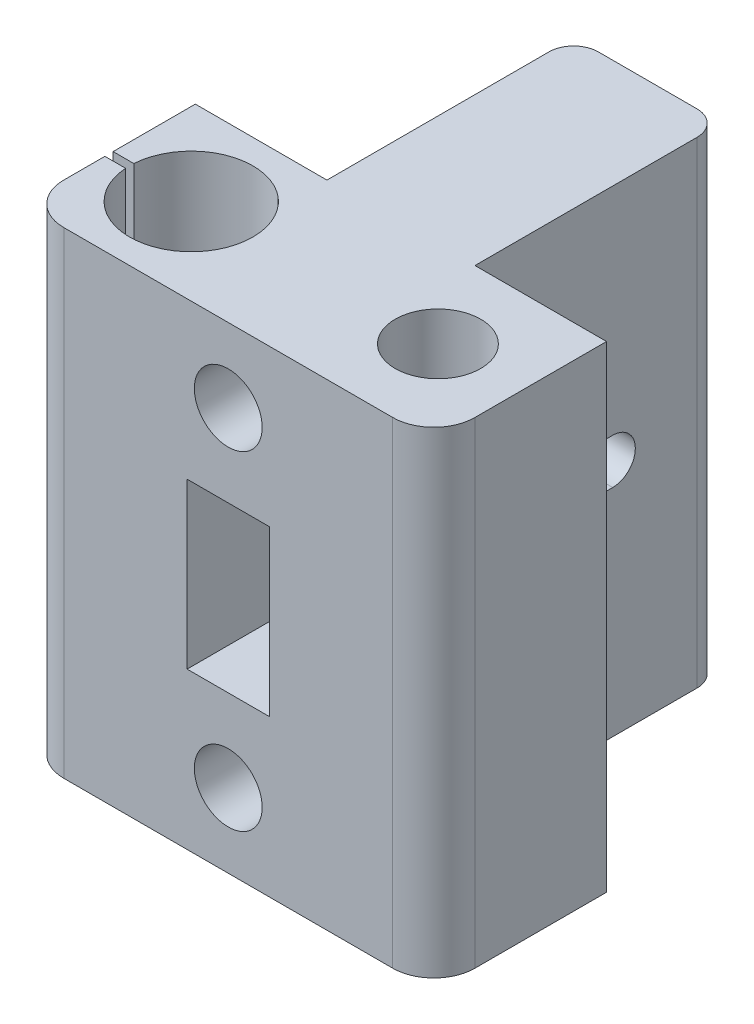
SolidWorks part; units mm, degrees
ref_plane "Front Plane" through (0, 0, 0) normal (0, 0, 1) x (1, 0, 0)
ref_plane "Top Plane" through (0, 0, 0) normal (0, 1, 0) x (1, 0, 0)
ref_plane "Right Plane" through (0, 0, 0) normal (1, 0, 0) x (0, 0, -1)
sketch "Sketch1" plane through (0, 0, 0) normal (0, 1, 0) x (1, 0, 0)
  line L1 (-25, 10.5) -> (25, 10.5)
  line L2 (-25, 10.5) -> (-25, -10.5)
  line L3 (-25, -10.5) -> (25, -10.5)
  line L4 (25, 10.5) -> (25, -10.5)
  line L5 (-25, 10.5) -> (25, -10.5) construction
  line L6 (-25, -10.5) -> (25, 10.5) construction
  point P0 (0, 0)
  dimension "D1" = 21
  dimension "D2" = 50
extrude "Boss-Extrude1" add sketch "Sketch1" along normal blind 58
sketch "Sketch3" plane through (0, 58, 0) normal (0, 1, 0) x (1, 0, 0)
  line L0 (-15, 0) -> (15, 0) construction
  circle A0 centre (-15, 0) radius 7.5
  dimension "D1" = 15
  dimension "D2" = 30
extrude "Cut-Extrude1" cut sketch "Sketch3" against normal blind 24 contours A0
sketch "Sketch4" plane through (0, 58, 0) normal (0, 1, 0) x (1, 0, 0)
  line L0 (-15, 0) -> (15, 0) construction
  circle A0 centre (15, 0) radius 5.2
  dimension "D1" = 10.4
extrude "Cut-Extrude2" cut sketch "Sketch4" against normal up to next
sketch "Sketch5" plane through (0, 0, 0) normal (0, -1, 0) x (1, 0, 0)
  circle A1 centre (-15, 0) radius 7.5
  circle A2 centre (-15, 0) radius 7.5
  dimension "D1" = 0
extrude "Cut-Extrude3" cut sketch "Sketch5" against normal blind 24
sketch "Sketch6" plane through (0, 0, 0) normal (0, -1, 0) x (1, 0, 0)
  circle A0 centre (-15, 0) radius 4.5
extrude "Cut-Extrude4" cut sketch "Sketch6" against normal up to next
sketch "Sketch8" plane through (0, 0, 10.5) normal (0, 0, 1) x (1, 0, 0)
  line L0 (-25, 29) -> (25, 29) construction
  line L1 (-25, 58) -> (-25, 0) construction
  line L2 (25, 58) -> (25, 0) construction
  line L3 (0, 58) -> (0, 0) construction
  line L4 (-25, 58) -> (25, 58) construction
  line L6 (-5, 19) -> (5, 19)
  line L7 (-5, 19) -> (-5, 39)
  line L8 (-5, 39) -> (5, 39)
  line L9 (5, 19) -> (5, 39)
  line L10 (-5, 19) -> (5, 39) construction
  line L11 (-5, 39) -> (5, 19) construction
  point P11 (0, 29)
  dimension "D1" = 20
  dimension "D2" = 10
extrude "Cut-Extrude5" cut sketch "Sketch8" against normal up to next
sketch "Sketch10" plane through (0, 0, -10.5) normal (0, 0, -1) x (-1, 0, 0)
  line L0 (-25, 29) -> (25, 29) construction
  line L1 (-25, 58) -> (-25, 0) construction
  line L2 (25, 58) -> (25, 0) construction
  line L3 (0, 58) -> (0, 0) construction
  line L4 (-25, 58) -> (25, 58) construction
sketch "Sketch11" plane through (0, 0, -10.5) normal (0, 0, -1) x (-1, 0, 0)
  line L0 (-25, 29) -> (25, 29) construction
  line L1 (9, 39) -> (5, 39)
  line L2 (9, 39) -> (9, 19)
  line L3 (9, 19) -> (5, 19)
  line L4 (5, 39) -> (5, 19)
  line L5 (9, 39) -> (5, 19) construction
  line L6 (9, 19) -> (5, 39) construction
  line L7 (0, 58) -> (0, 0) construction
  line L8 (0, 58) -> (0, 0)
  line L9 (-9, 19) -> (-5, 19)
  line L10 (-5, 39) -> (-5, 19)
  line L11 (-9, 39) -> (-5, 39)
  line L12 (-9, 39) -> (-9, 19)
  point P0 (7, 29)
  line M7 (-5, 19) -> (-5, 39)
  line M9 (5, 39) -> (5, 19)
  dimension "D1" = 5
  dimension "D2" = 4
  dimension "D3" = 20
extrude "Boss-Extrude2" add sketch "Sketch11" along normal blind 26 contours L1 L4 L3 L2 M9 | L11 L12 L9 L10 M7 region at (-7, 29, -10.5) region at (7, 29, -10.5)
sketch "Sketch12" plane through (0, 0, -36.5) normal (0, 0, -1) x (-1, 0, 0)
  line L1 (9, 19) -> (-9, 19)
  line L2 (9, 19) -> (9, 39)
  line L3 (9, 39) -> (-9, 39)
  line L4 (-9, 19) -> (-9, 39)
extrude "Boss-Extrude3" add sketch "Sketch12" along normal blind 4
sketch "Sketch13" plane through (9, 0, 0) normal (1, 0, 0) x (0, 0, -1)
  line L3 (10.5, 29) -> (40.5, 29) construction
  line L4 (10.5, 39) -> (10.5, 19) construction
  line L5 (40.5, 39) -> (40.5, 19) construction
  line L6 (18.25, 29) -> (27.25, 29) construction
  line L7 (18.25, 31.75) -> (27.25, 31.75)
  line L8 (18.25, 26.25) -> (27.25, 26.25)
  arc A0 (18.25, 31.75) -> (18.25, 26.25) centre (18.25, 29) ccw
  arc A1 (27.25, 26.25) -> (27.25, 31.75) centre (27.25, 29) ccw
  point P1 (15.5, 29)
  point P14 (22.75, 29)
  dimension "D1" = 5.5
  dimension "D2" = 5
  dimension "D3" = 9
extrude "Cut-Extrude7" cut sketch "Sketch13" against normal through all
fillet "Fillet1" radius 5 2 edges at (-25, 29, 10.5) (25, 29, 10.5)
sketch "Sketch14" plane through (0, 0, 0) normal (0, -1, 0) x (1, 0, 0)
  line L0 (20.5508, 5.5508) -> (9.4492, -5.5508) construction
  line L1 (25, -10.5) -> (-25, -10.5) construction
  circle A0 centre (20.5508, 5.5508) radius 1.95
  circle A1 centre (15, 0) radius 5.2 construction
  circle A2 centre (9.4492, -5.5508) radius 1.95
  circle A3 centre (15, 0) radius 5.2 construction
  dimension "D1" = 7.85
  dimension "D2" = 3.9
  dimension "D3" = 3.9
  dimension "D4" = 7.85
  dimension "D5" = 45
extrude "Cut-Extrude8" cut sketch "Sketch14" against normal blind 10
sketch "Sketch15" plane through (0, 58, 0) normal (0, 1, 0) x (1, 0, 0)
  line L0 (-25, 10.5) -> (-25, -5.5) construction
  line L1 (-25, -0.5) -> (-19.4721, -0.5)
  line L2 (-25, -0.5) -> (-25, 0.5)
  line L3 (-25, 0.5) -> (-19.4721, 0.5)
  line L4 (-19.4721, -0.5) -> (-19.4721, 0.5)
  circle A2 centre (-15, 0) radius 4.5 construction
  dimension "D1" = 1
extrude "Cut-Extrude9" cut sketch "Sketch15" against normal through all
sketch "Sketch17" plane through (9, 0, 0) normal (1, 0, 0) x (0, 0, -1)
  line L0 (10.5, 39) -> (10.5, 58)
  line L1 (10.5, 58) -> (40.5, 58)
  line L2 (40.5, 58) -> (40.5, 39)
  line L3 (40.5, 39) -> (10.5, 39)
  line L4 (10.5, 19) -> (10.5, 0)
  line L5 (10.5, 0) -> (40.5, 0)
  line L6 (40.5, 0) -> (40.5, 19)
  line L7 (40.5, 19) -> (10.5, 19)
extrude "Boss-Extrude5" add sketch "Sketch17" against normal up to surface (18 mm away) up to face at (-9, 29, -22.75)
sketch "Sketch7" plane through (0, 0, 10.5) normal (0, 0, 1) x (1, 0, 0)
  line L0 (0, 58) -> (0, 0) construction
  line L1 (-20, 58) -> (20, 58) construction
  line L2 (-20, 0) -> (20, 0) construction
  line L3 (-25, 29) -> (25, 29) construction
  line L4 (-25, 58) -> (-25, 0) construction
  line L5 (25, 58) -> (25, 0) construction
  circle A1 centre (0, 49) radius 4.125
  circle A2 centre (0, 9) radius 4.125
  point P24 (0, 9)
  dimension "D1" = 8.25
  dimension "D2" = 9
extrude "Cut-Extrude6" cut sketch "Sketch7" against normal blind 45
fillet "Fillet8" radius 3 2 edges at (-9, 29, -40.5) (9, 29, -40.5)
sketch "Sketch18" plane through (0, 0, -40.5) normal (0, 0, -1) x (-1, 0, 0)
  line L0 (-3, 26.25) -> (3, 26.25)
  line L1 (3, 26.25) -> (3, 31.75)
  line L2 (3, 31.75) -> (-3, 31.75)
  line L3 (-3, 31.75) -> (-3, 26.25)
  line L4 (-5, 26.25) -> (-9, 26.25) construction
  line L6 (6, 0) -> (6, 58) construction
  dimension "D1" = 5.5
  dimension "D2" = 6
  dimension "D3" = 3
extrude "Cut-Extrude10" cut sketch "Sketch18" against normal blind 1 contours L2 L3 L0 L1
